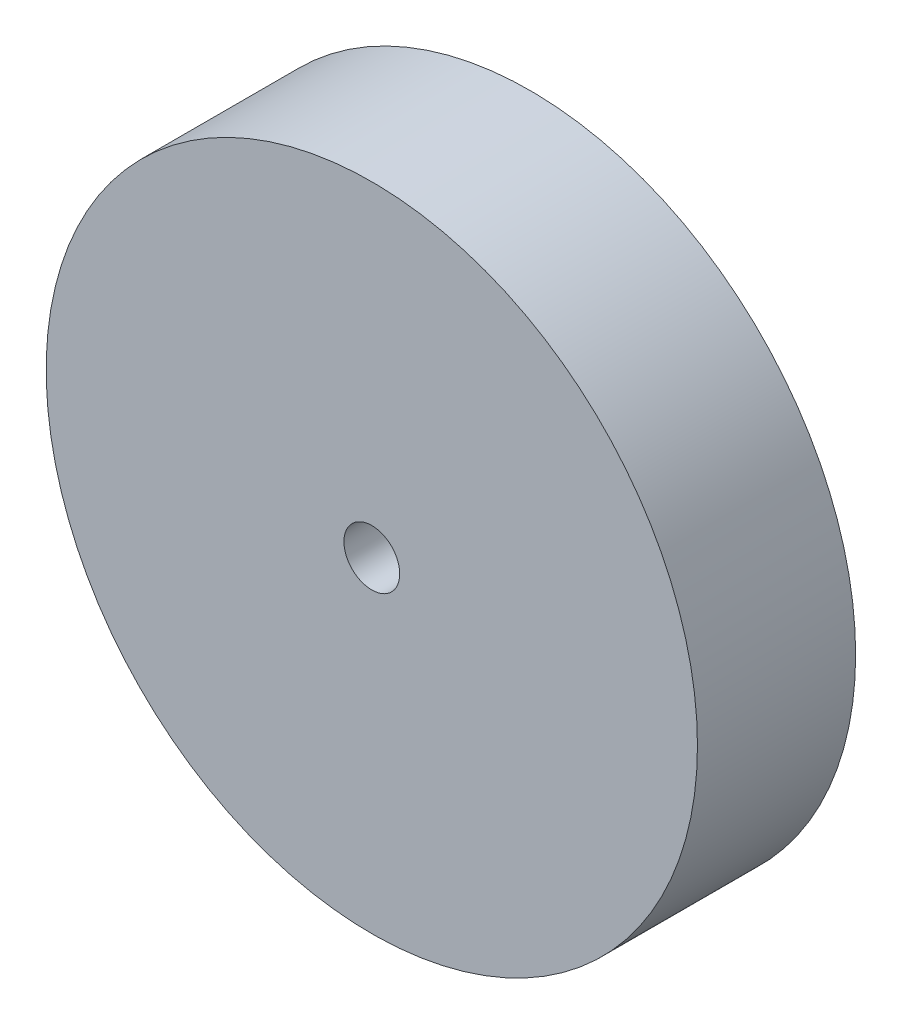
SolidWorks part; units mm, degrees
ref_plane "Front Plane" through (0, 0, 0) normal (0, 0, 1) x (1, 0, 0)
ref_plane "Top Plane" through (0, 0, 0) normal (0, 1, 0) x (1, 0, 0)
ref_plane "Right Plane" through (0, 0, 0) normal (1, 0, 0) x (0, 0, -1)
sketch "Sketch1" plane through (0, 0, 0) normal (0, 0, 1) x (1, 0, 0)
  circle A0 centre (0, 0) radius 18
extrude "Boss-Extrude1" add sketch "Sketch1" along normal blind 20
sketch "Sketch2" plane through (0, 0, 20) normal (0, 0, 1) x (1, 0, 0)
  circle A0 centre (0, 0) radius 3
extrude "Cut-Extrude1" cut sketch "Sketch2" against normal blind 60
sketch "Sketch4" plane through (0, 0, 20) normal (0, 0, 1) x (1, 0, 0)
  circle A0 centre (0, 0) radius 14.576
  circle A1 centre (0, 0) radius 35
extrude "Boss-Extrude2" add sketch "Sketch4" against normal blind 17
